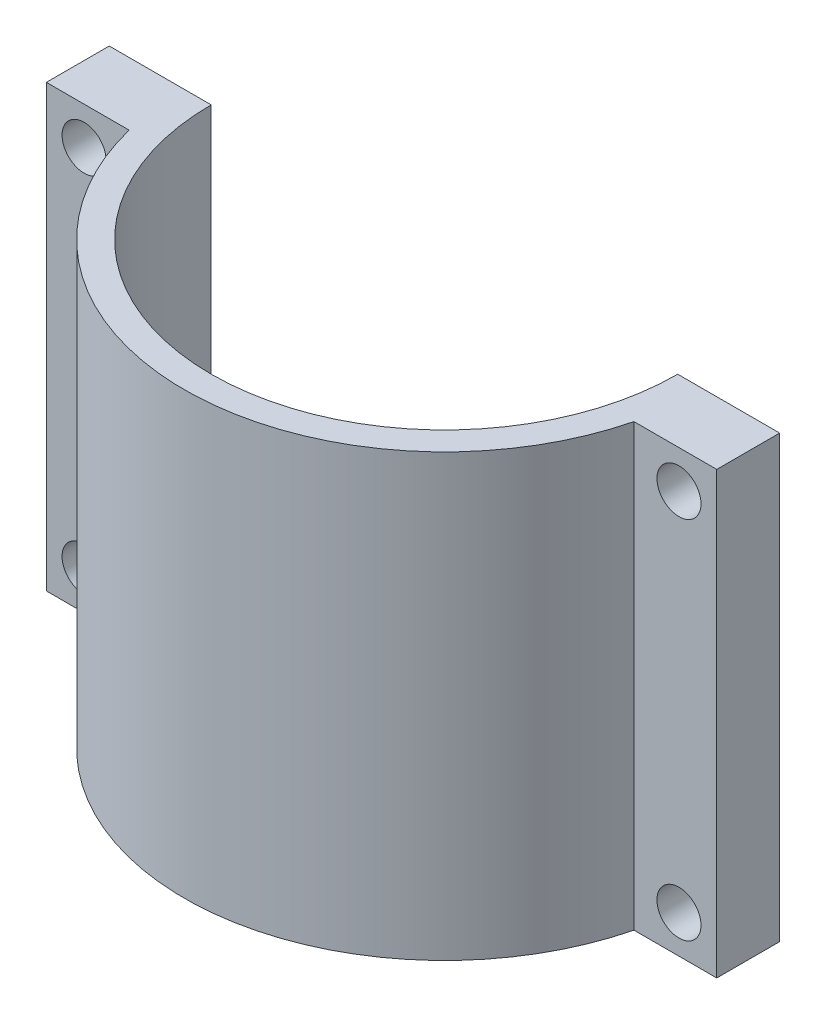
SolidWorks part; units mm, degrees
ref_plane "Front Plane" through (0, 0, 0) normal (0, 0, 1) x (1, 0, 0)
ref_plane "Top Plane" through (0, 0, 0) normal (0, 1, 0) x (1, 0, 0)
ref_plane "Right Plane" through (0, 0, 0) normal (1, 0, 0) x (0, 0, -1)
sketch "Sketch1" plane through (0, 0, 0) normal (0, 0, 1) x (1, 0, 0)
  line L0 (0, 0) -> (0, -2) construction
  line L1 (-3, 3) -> (5.1, 3)
  line L2 (-3, 3) -> (-3, -26)
  line L5 (-3, 3) -> (3, -3) construction
  line L6 (-3, -3) -> (3, 3) construction
  line L7 (50.27, 3) -> (42.17, 3)
  line L8 (50.27, 3) -> (50.27, -26)
  line L11 (50.27, 3) -> (44.27, -3) construction
  line L12 (50.27, -3) -> (44.27, 3) construction
  line L13 (0, -14.5) -> (47.2758, -14.5) construction
  line L14 (50.27, -26) -> (44.27, -32) construction
  line L15 (50.27, -32) -> (44.27, -26) construction
  line L16 (-3, -26) -> (3, -32) construction
  line L17 (-3, -32) -> (3, -26) construction
  line L20 (50.27, -32) -> (50.27, -26)
  line L21 (50.27, -32) -> (42.17, -32)
  line L24 (-3, -32) -> (-3, -26)
  line L25 (-3, -32) -> (5.1, -32)
  line L26 (5.1, 3) -> (5.1, -32)
  line L27 (0, -27) -> (0, -29) construction
  line L28 (42.17, 3) -> (42.17, -32)
  circle A0 centre (0, 0) radius 2 construction
  circle A1 centre (47.27, 0) radius 2 construction
  circle A2 centre (0, 0) radius 1.75
  circle A3 centre (47.27, 0) radius 1.75
  circle A4 centre (47.27, -29) radius 2 construction
  circle A5 centre (0, -29) radius 2 construction
  circle A6 centre (47.27, -29) radius 1.75
  circle A7 centre (0, -29) radius 1.75
  dimension "D1" = 47.27
  dimension "D3" = 4
  dimension "D2" = 6
  dimension "D4" = 6
extrude "Boss-Extrude1" add sketch "Sketch1" along normal blind 5
sketch "Sketch2" plane through (0, 3, 0) normal (0, 1, 0) x (1, 0, 0)
  line L0 (42.17, 0) -> (44.305, 0)
  line L1 (-3, -18) -> (50.27, -18) construction
  line L2 (2.965, 0) -> (5.1, 0)
  arc A0 (5.1, 0) -> (42.17, 0) centre (23.635, 0) ccw
  arc A2 (2.965, 0) -> (44.305, 0) centre (23.635, 0) ccw
  point P14 (23.635, -2.5)
extrude "Boss-Extrude2" add sketch "Sketch1<2>" along normal blind 5
sketch "Sketch1<2>" plane through (0, 0, 0) normal (0, 0, 1) x (1, 0, 0) same geometry as "Sketch1"
extrude "Boss-Extrude3" add sketch "Sketch2" against normal up to surface (35 mm away) up to face at (1.05, -32, 2.5)
